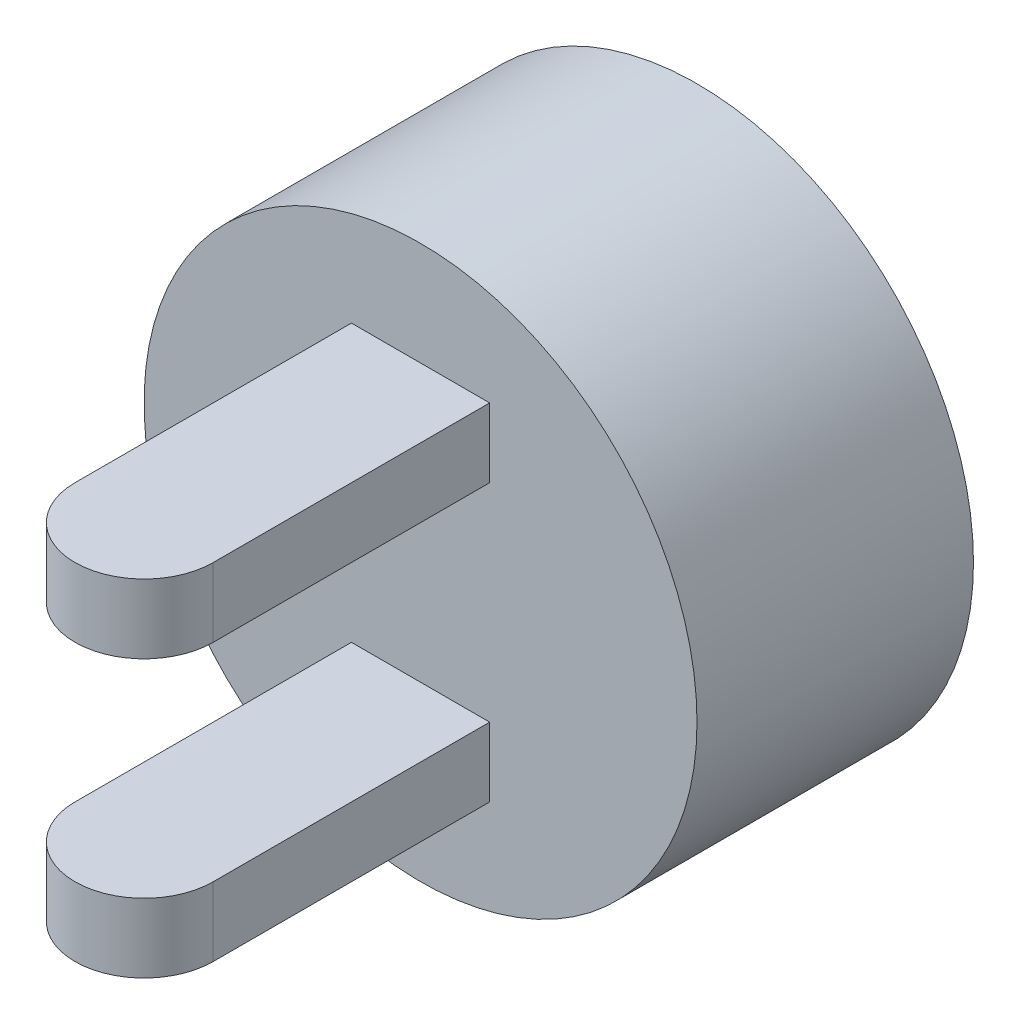
SolidWorks part; units mm, degrees
ref_plane "Front Plane" through (0, 0, 0) normal (0, 0, 1) x (1, 0, 0)
ref_plane "Top Plane" through (0, 0, 0) normal (0, 1, 0) x (1, 0, 0)
ref_plane "Right Plane" through (0, 0, 0) normal (1, 0, 0) x (0, 0, -1)
sketch "Sketch1" plane through (0, 0, 0) normal (0, 0, 1) x (1, 0, 0)
  circle A0 centre (0, 0) radius 200
  circle A1 centre (0, 0) radius 200 construction
extrude "Boss-Extrude1" add sketch "Sketch1" along normal blind 200
sketch "Sketch2" plane through (0, 0, 0) normal (0, 1, 0) x (1, 0, 0)
  line L0 (0, -1000) -> (0, 49000) construction
  line L1 (-50, -200) -> (-50, -400)
  line L2 (-200, -200) -> (200, -200) construction
  line L3 (-50, -200) -> (50, -200)
  line L4 (50, -200) -> (50, -400)
  arc A0 (-50, -400) -> (50, -400) centre (0, -400) ccw
  point P10 (0, -200)
  dimension "D1" = 100
  dimension "D2" = 200
extrude "Boss-Extrude2" add sketch "Sketch2" along normal blind 50 from offset 75
extrude "Boss-Extrude3" add sketch "Sketch2<2>" against normal blind 50 from offset 75 contours L1 A0 L4 L3 offset against normal yes
sketch "Sketch2<2>" plane through (0, 0, 0) normal (0, 1, 0) x (1, 0, 0) same geometry as "Sketch2"
ref_point "Point1"
ref_plane "Plane1" through (0, 0, 400) normal (0, 0, 1) x (1, 0, 0)
sketch3d "3DSketch1"
  line L0 (0, 0, 400) -> (490.595, 0, 400) construction
  line L1 (0, 0, 400) -> (0, 409.6984, 400)
